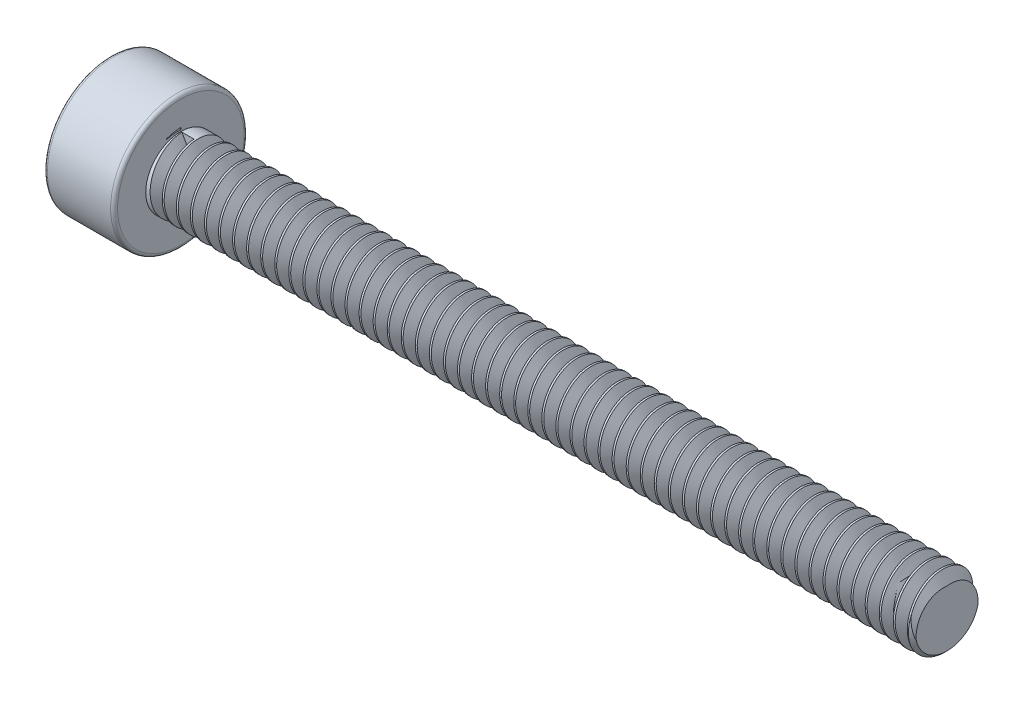
SolidWorks part; units mm, degrees
material "Cast Carbon Steel"
ref_plane "Front Plane" through (0, 0, 0) normal (0, 0, 1) x (1, 0, 0)
ref_plane "Top Plane" through (0, 0, 0) normal (0, 1, 0) x (1, 0, 0)
ref_plane "Right Plane" through (0, 0, 0) normal (1, 0, 0) x (0, 0, -1)
sketch "Sketch1" plane through (0, 0, 0) normal (0, 0, 1) x (1, 0, 0)
  line L0 (0, 0) -> (-85.5263, 0) construction
  line L1 (0, 0) -> (0, 1.8)
  line L2 (-0.1, 1.9) -> (-1.9, 1.9)
  line L3 (-2, 1.8) -> (-2, 0)
  line L4 (-2, 0) -> (0, 0)
  arc A0 (-1.9, 1.9) -> (-2, 1.8) centre (-1.9, 1.8) ccw
  arc A1 (0, 1.8) -> (-0.1, 1.9) centre (-0.1, 1.8) ccw
  dimension "head-round" = 0.1
  dimension "head-dia" = 3.8
  dimension "head-hight" = 2
revolve "Revolve1" add sketch "Sketch1" angle 360 about L0
sketch "Sketch2" plane through (-2, 0, 0) normal (-1, 0, 0) x (0, 0, 1)
  line L1 (0.866, 0) -> (0.433, 0.75)
  line L2 (0.433, 0.75) -> (-0.433, 0.75)
  line L3 (-0.433, 0.75) -> (-0.866, 0)
  line L4 (-0.866, 0) -> (-0.433, -0.75)
  line L5 (-0.433, -0.75) -> (0.433, -0.75)
  line L6 (0.433, -0.75) -> (0.866, 0)
  circle A0 centre (0, 0) radius 0.75 construction
  dimension "NV" = 1.5
extrude "Extrude1" cut sketch "Sketch2" against normal blind 1
sketch "Sketch3" plane through (0, 0, 0) normal (0, 0, 1) x (1, 0, 0)
  line L0 (0, 0) -> (4.4714, 0) construction
  line L1 (21.8, 0.9) -> (21.7, 1)
  line L2 (0, 0) -> (21.8, 0)
  line L3 (0, 0) -> (0, 1)
  line L4 (0, 1) -> (21.7, 1)
  line L5 (21.8, 0) -> (21.8, 0.9)
  point P3 (21.8, 1)
  dimension "45-cut" = 0.1
  dimension "D2" = 45
  dimension "lenght" = 21.8
  dimension "M" = 2
revolve "Revolve2" add sketch "Sketch3" angle 360 about L0
sketch "Sketch4" plane through (0, 0, 0) normal (0, 0, 1) x (1, 0, 0)
  line L0 (21.9691, 1.1) -> (22.2, 0.7)
  line L1 (22.2, 0.7) -> (22.4309, 1.1)
  line L2 (22.4309, 1.1) -> (21.9691, 1.1)
  line L3 (22.2, 0.4371) -> (22.2, 1.3714) construction
  line L4 (21.8, -0.9) -> (21.8, 0.9) construction
  line L5 (0, 0) -> (4.3833, 0) construction
  dimension "D1" = 60
  dimension "D2" = 30
  dimension "cut-pith1" = 0.4
  dimension "cut-dia" = 1.4
  dimension "pith1" = 0.4
sketch "Sketch5" plane through (21.8, 0, 0) normal (1, 0, 0) x (0, 0, -1)
  circle A0 centre (0, 0) radius 1
  dimension "helix-dim" = 2
curve "Helix/Spiral1" pitch 0.4 height 22 turns 55
sweep "Cut-Sweep2" cut profiles "Sketch4" path "Helix/Spiral1" align with end faces yes
